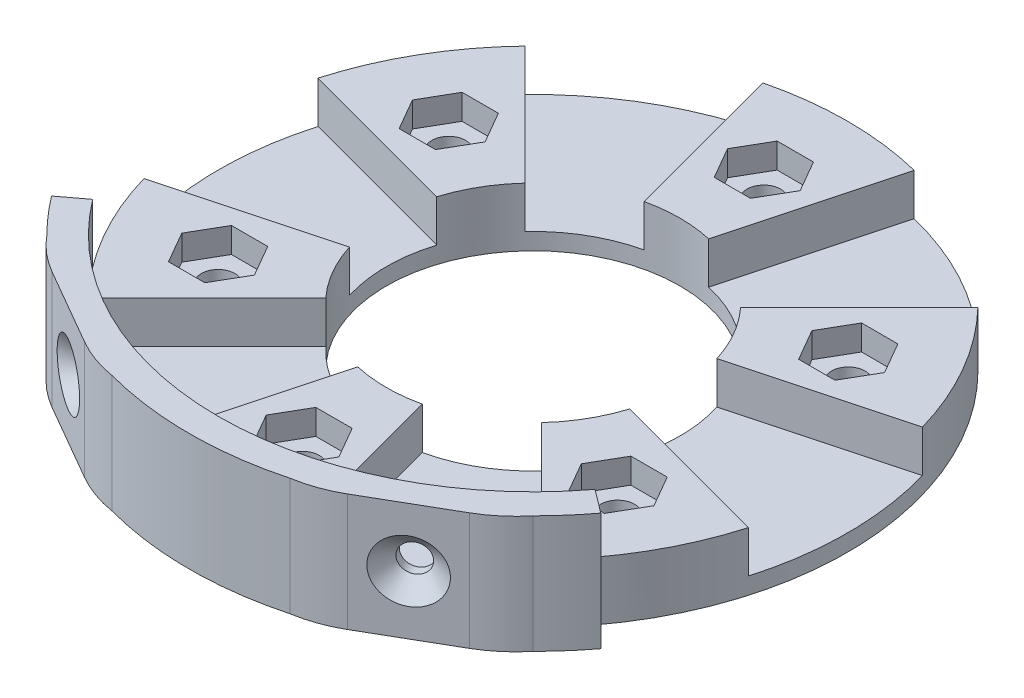
SolidWorks part; units mm, degrees
ref_plane "Front" through (0, 0, 0) normal (0, 0, 1) x (1, 0, 0)
ref_plane "Top" through (0, 0, 0) normal (0, 1, 0) x (1, 0, 0)
ref_plane "Right" through (0, 0, 0) normal (1, 0, 0) x (0, 0, -1)
sketch "Sketch1" plane through (0, 0, 0) normal (0, 1, 0) x (1, 0, 0)
  line L0 (21.6506, 17.5) -> (19.4856, 13.75)
  line L1 (4.3301, 27.5) -> (2.1651, 31.25)
  line L2 (2.1651, 31.25) -> (-2.1651, 31.25)
  line L3 (-2.1651, 31.25) -> (-4.3301, 27.5)
  line L4 (-4.3301, 27.5) -> (-2.1651, 23.75)
  line L5 (-2.1651, 23.75) -> (2.1651, 23.75)
  line L6 (2.1651, 23.75) -> (4.3301, 27.5)
  line L7 (25.9808, 17.5) -> (21.6506, 17.5)
  line L8 (28.1458, 13.75) -> (25.9808, 17.5)
  line L9 (25.9808, 10) -> (28.1458, 13.75)
  line L10 (19.4856, 13.75) -> (21.6506, 10)
  line L11 (21.6506, 10) -> (25.9808, 10)
  line L12 (25.9808, -10) -> (21.6506, -10)
  line L13 (28.1458, -13.75) -> (25.9808, -10)
  line L14 (25.9808, -17.5) -> (28.1458, -13.75)
  line L15 (21.6506, -17.5) -> (25.9808, -17.5)
  line L16 (21.6506, -10) -> (19.4856, -13.75)
  line L17 (19.4856, -13.75) -> (21.6506, -17.5)
  line L18 (4.3301, -27.5) -> (2.1651, -23.75)
  line L19 (2.1651, -31.25) -> (4.3301, -27.5)
  line L20 (-2.1651, -31.25) -> (2.1651, -31.25)
  line L21 (-4.3301, -27.5) -> (-2.1651, -31.25)
  line L22 (2.1651, -23.75) -> (-2.1651, -23.75)
  line L23 (-2.1651, -23.75) -> (-4.3301, -27.5)
  line L24 (-21.6506, -17.5) -> (-19.4856, -13.75)
  line L25 (-25.9808, -17.5) -> (-21.6506, -17.5)
  line L26 (-28.1458, -13.75) -> (-25.9808, -17.5)
  line L27 (-25.9808, -10) -> (-28.1458, -13.75)
  line L28 (-19.4856, -13.75) -> (-21.6506, -10)
  line L29 (-21.6506, -10) -> (-25.9808, -10)
  line L30 (-25.9808, 10) -> (-21.6506, 10)
  line L31 (-28.1458, 13.75) -> (-25.9808, 10)
  line L32 (-25.9808, 17.5) -> (-28.1458, 13.75)
  line L33 (-21.6506, 17.5) -> (-25.9808, 17.5)
  line L34 (-21.6506, 10) -> (-19.4856, 13.75)
  line L35 (-19.4856, 13.75) -> (-21.6506, 17.5)
  line L36 (23.8157, 13.75) -> (15.1554, 8.75)
  line L37 (23.8157, 13.75) -> (32.476, 18.75)
  line L38 (0, 0) -> (9.7057, 36.2222)
  line L39 (0, 0) -> (26.5165, 26.5165)
  line L40 (-9.0279, 36.3971) -> (-3.8496, 17.0713)
  line L41 (26.5165, 26.5165) -> (23.8157, 13.75)
  line L42 (0, 0) -> (36.2222, 9.7057)
  line L43 (0, 0) -> (36.2222, -9.7057)
  line L44 (0, 0) -> (26.5165, -26.5165)
  line L45 (0, 0) -> (9.7057, -36.2222)
  line L46 (0, 0) -> (-9.7057, -36.2222)
  line L47 (0, 0) -> (-26.5165, -26.5165)
  line L48 (0, 0) -> (-36.2222, -9.7057)
  line L49 (0, 0) -> (-36.2222, 9.7057)
  line L50 (0, 0) -> (-26.5165, 26.5165)
  line L51 (0, 0) -> (-9.7057, 36.2222)
  line L52 (0, 0) -> (0, 37.5)
  line L53 (9.0279, 36.3971) -> (3.8496, 17.0713)
  line L54 (27.0069, 26.0169) -> (12.8594, 11.8695)
  line L55 (36.0347, 10.3802) -> (16.709, 5.2019)
  line L56 (36.0347, -10.3802) -> (16.709, -5.2019)
  line L57 (27.0069, -26.0169) -> (12.8594, -11.8695)
  line L58 (9.0279, -36.3971) -> (3.8496, -17.0713)
  line L59 (-9.0279, -36.3971) -> (-3.8496, -17.0713)
  line L60 (-27.0069, -26.0169) -> (-12.8594, -11.8695)
  line L61 (-36.0347, -10.3802) -> (-16.709, -5.2019)
  line L62 (-36.0347, 10.3802) -> (-16.709, 5.2019)
  line L63 (-27.0069, 26.0169) -> (-12.8594, 11.8695)
  circle A0 centre (0, 27.5) radius 2.15
  circle A1 centre (0, 0) radius 37.5
  circle A2 centre (0, 27.5) radius 3.75 construction
  circle A3 centre (23.8157, 13.75) radius 3.75 construction
  circle A4 centre (23.8157, 13.75) radius 2.15
  circle A5 centre (23.8157, -13.75) radius 3.75 construction
  circle A6 centre (23.8157, -13.75) radius 2.15
  circle A7 centre (0, -27.5) radius 3.75 construction
  circle A8 centre (0, -27.5) radius 2.15
  circle A9 centre (-23.8157, -13.75) radius 3.75 construction
  circle A10 centre (-23.8157, -13.75) radius 2.15
  circle A11 centre (-23.8157, 13.75) radius 3.75 construction
  circle A12 centre (-23.8157, 13.75) radius 2.15
  circle A13 centre (0, 0) radius 17.5
  point P60 (0, 0)
  point P75 (0, 0)
  point P101 (0, 0)
  dimension "D1" = 4.3
  dimension "D2" = 75
  dimension "D4" = 7.5
  dimension "D6" = 35
  dimension "D3" = 27.5
  dimension "D7" = 23.8157
  dimension "D8" = 15
  dimension "D10" = 0.7
  dimension "D11" = 0.7
  dimension "D12" = 15
  dimension "D5" = 6
  dimension "D9" = 6
  dimension "D13" = 6
extrude "Boss-Extrude2" add sketch "Sketch1" along normal blind 3 contours A13 L52 L5 L4 L3 L2 A1 L40 | A13 L53 A1 L52 L2 L1 L6 L5 | A13 L63 A1 L62 L35 L34 L30 L31 L32 L33 | A13 L36 L10 L0 L7 L41 L54 | A13 L55 A1 L37 L8 L9 L11 L10 L36 | L37 A1 L54 L41 L7 L8 | A13 L57 A1 L56 L17 L16 L12 L13 L14 L15 | A13 L59 A1 L58 L23 L22 L18 L19 L20 L21 | A13 L61 A1 L60 L29 L28 L24 L25 L26 L27
sketch "Sketch2" plane through (0, 0, 0) normal (0, -1, 0) x (-1, 0, 0)
  line L12 (16.709, 5.2019) -> (36.0347, 10.3802) construction
  line L13 (27.0069, 26.0169) -> (12.8594, 11.8695) construction
  line L14 (3.8496, 17.0713) -> (9.0279, 36.3971) construction
  line L15 (-9.0279, 36.3971) -> (-3.8496, 17.0713) construction
  line L16 (-36.0347, 10.3802) -> (-16.709, 5.2019) construction
  line L17 (-12.8594, 11.8695) -> (-27.0069, 26.0169) construction
  line L18 (-16.709, -5.2019) -> (-36.0347, -10.3802) construction
  line L19 (-27.0069, -26.0169) -> (-12.8594, -11.8695) construction
  line L20 (-3.8496, -17.0713) -> (-9.0279, -36.3971) construction
  line L21 (9.0279, -36.3971) -> (3.8496, -17.0713) construction
  line L22 (12.8594, -11.8695) -> (27.0069, -26.0169) construction
  line L23 (36.0347, -10.3802) -> (16.709, -5.2019) construction
  line L24 (16.709, 5.2019) -> (36.0347, 10.3802)
  line L25 (27.0069, 26.0169) -> (12.8594, 11.8695)
  line L26 (3.8496, 17.0713) -> (9.0279, 36.3971)
  line L27 (-9.0279, 36.3971) -> (-3.8496, 17.0713)
  line L28 (-36.0347, 10.3802) -> (-16.709, 5.2019)
  line L29 (-12.8594, 11.8695) -> (-27.0069, 26.0169)
  line L30 (-16.709, -5.2019) -> (-36.0347, -10.3802)
  line L31 (-27.0069, -26.0169) -> (-12.8594, -11.8695)
  line L32 (-3.8496, -17.0713) -> (-9.0279, -36.3971)
  line L33 (9.0279, -36.3971) -> (3.8496, -17.0713)
  line L34 (12.8594, -11.8695) -> (27.0069, -26.0169)
  line L35 (36.0347, -10.3802) -> (16.709, -5.2019)
  circle A0 centre (0, 0) radius 37.5
  circle A1 centre (0, 0) radius 17.5
  circle A2 centre (0, 27.5) radius 2
  circle A3 centre (23.8157, 13.75) radius 2
  circle A4 centre (23.8157, -13.75) radius 2
  circle A5 centre (0, -27.5) radius 2
  circle A6 centre (-23.8157, -13.75) radius 2
  circle A7 centre (-23.8157, 13.75) radius 2
  arc A8 (16.709, 5.2019) -> (12.8594, 11.8695) centre (0, 0) ccw construction
  arc A9 (36.0347, 10.3802) -> (27.0069, 26.0169) centre (0, 0) ccw construction
  arc A10 (3.8496, 17.0713) -> (-3.8496, 17.0713) centre (0, 0) ccw construction
  arc A11 (9.0279, 36.3971) -> (-9.0279, 36.3971) centre (0, 0) ccw construction
  arc A12 (-12.8594, 11.8695) -> (-16.709, 5.2019) centre (0, 0) ccw construction
  arc A13 (-27.0069, 26.0169) -> (-36.0347, 10.3802) centre (0, 0) ccw construction
  arc A14 (-16.709, -5.2019) -> (-12.8594, -11.8695) centre (0, 0) ccw construction
  arc A15 (-36.0347, -10.3802) -> (-27.0069, -26.0169) centre (0, 0) ccw construction
  arc A16 (-3.8496, -17.0713) -> (3.8496, -17.0713) centre (0, 0) ccw construction
  arc A17 (-9.0279, -36.3971) -> (9.0279, -36.3971) centre (0, 0) ccw construction
  arc A18 (12.8594, -11.8695) -> (16.709, -5.2019) centre (0, 0) ccw construction
  arc A19 (27.0069, -26.0169) -> (36.0347, -10.3802) centre (0, 0) ccw construction
  arc A20 (16.709, 5.2019) -> (12.8594, 11.8695) centre (0, 0) ccw
  arc A21 (36.0347, 10.3802) -> (27.0069, 26.0169) centre (0, 0) ccw
  arc A22 (3.8496, 17.0713) -> (-3.8496, 17.0713) centre (0, 0) ccw
  arc A23 (9.0279, 36.3971) -> (-9.0279, 36.3971) centre (0, 0) ccw
  arc A24 (-12.8594, 11.8695) -> (-16.709, 5.2019) centre (0, 0) ccw
  arc A25 (-27.0069, 26.0169) -> (-36.0347, 10.3802) centre (0, 0) ccw
  arc A26 (-16.709, -5.2019) -> (-12.8594, -11.8695) centre (0, 0) ccw
  arc A27 (-36.0347, -10.3802) -> (-27.0069, -26.0169) centre (0, 0) ccw
  arc A28 (-3.8496, -17.0713) -> (3.8496, -17.0713) centre (0, 0) ccw
  arc A29 (-9.0279, -36.3971) -> (9.0279, -36.3971) centre (0, 0) ccw
  arc A30 (12.8594, -11.8695) -> (16.709, -5.2019) centre (0, 0) ccw
  arc A31 (27.0069, -26.0169) -> (36.0347, -10.3802) centre (0, 0) ccw
  point P18 (0, 0)
  dimension "D1" = 4
  dimension "D4" = 75
  dimension "D5" = 35
  dimension "D2" = 27.5
  dimension "D6" = 23.8157
  dimension "D7" = 13.75
  dimension "D3" = 6
extrude "Boss-Extrude3" add sketch "Sketch2" along normal blind 2
sketch "Sketch3" plane through (0, -2, 0) normal (0, -1, 0) x (-1, 0, 0)
  circle A0 centre (0, 0) radius 37.5
  circle A1 centre (0, 0) radius 17.5
  circle A2 centre (0, 27.5) radius 2
  circle A3 centre (23.8157, 13.75) radius 2
  circle A4 centre (23.8157, -13.75) radius 2
  circle A5 centre (0, -27.5) radius 2
  circle A6 centre (-23.8157, -13.75) radius 2
  circle A7 centre (-23.8157, 13.75) radius 2
  point P19 (0, 0)
  dimension "D1" = 6
extrude "Boss-Extrude4" add sketch "Sketch3" along normal blind 2
sketch "Sketch4" plane through (0, -4, 0) normal (0, -1, 0) x (-1, 0, 0)
  line L0 (0, 0) -> (32.7404, -24.6793)
  line L1 (0, 0) -> (-32.7404, -24.6793)
  line L2 (28.9914, -28.9914) -> (0, 0)
  line L3 (-28.9914, -28.9914) -> (0, 0)
  line L6 (0, 0) -> (10.6116, -39.603)
  line L7 (0, 0) -> (-10.6116, -39.603)
  line L10 (10.6116, -39.603) -> (10.8704, -40.5689)
  line L11 (28.9914, -28.9914) -> (29.6985, -29.6985)
  line L12 (-10.6116, -39.603) -> (-10.8704, -40.5689)
  line L13 (-28.9914, -28.9914) -> (-29.6985, -29.6985)
  line L14 (-29.6985, -29.6985) -> (-10.8704, -40.5689)
  line L15 (10.8704, -40.5689) -> (29.6985, -29.6985)
  line L16 (-27.0069, -26.0169) -> (-12.8594, -11.8695) construction
  line L17 (12.8594, -11.8695) -> (27.0069, -26.0169) construction
  line L18 (-3.8496, -17.0713) -> (-9.0279, -36.3971) construction
  line L19 (9.0279, -36.3971) -> (3.8496, -17.0713) construction
  circle A0 centre (0, 0) radius 37.5
  circle A1 centre (0, 0) radius 41
  dimension "D1" = 82
  dimension "D2" = 75
  dimension "D3" = 5
  dimension "D4" = 5
  dimension "D5" = 1
  dimension "D6" = 1
  dimension "D7" = 1
  dimension "D8" = 1
extrude "Boss-Extrude5" add sketch "Sketch4" against normal blind 14
fillet "Fillet1" radius 15 4 edges at (29.6985, 3, 29.6985) (10.8704, 3, 40.5689) (-29.6985, 3, 29.6985) (-10.8704, 3, 40.5689)
sketch "Sketch6" plane through (20.2844, 0, 35.1337) normal (0.5, 0, 0.866) x (0.866, 0, -0.5)
  line L1 (0, 3) -> (0, 10)
  line L2 (5.3159, 10) -> (-5.3159, 10) construction
  line L4 (0, 3) -> (-5.3159, 3)
  line L5 (0, 3) -> (0, -4)
  line L6 (5.3159, -4) -> (-5.3159, -4) construction
  line L7 (-5.3159, 10) -> (-5.3159, -4) construction
  line L8 (0, 3) -> (5.3159, 3)
  line L9 (5.3159, -4) -> (5.3159, 10) construction
  circle A0 centre (0, 3) radius 1.65
  dimension "D1" = 3.3
extrude "Cut-Extrude1" cut sketch "Sketch6" against normal blind 4 contours L5 A0 L8 | L4 A0 L5 | L8 A0 L1 | L1 A0 L4
sketch "Sketch7" plane through (-20.2844, 0, 35.1337) normal (-0.5, 0, 0.866) x (0.866, 0, 0.5)
  line L1 (0, 3) -> (0, 10)
  line L4 (5.3159, 10) -> (-5.3159, 10) construction
  line L8 (0, 3) -> (0, -4)
  line L9 (5.3159, -4) -> (-5.3159, -4) construction
  line L10 (0, 3) -> (-5.3159, 3)
  line L11 (-5.3159, 10) -> (-5.3159, -4) construction
  line L12 (0, 3) -> (5.3159, 3)
  line L13 (5.3159, -4) -> (5.3159, 10) construction
  line L15 (10.3802, -2) -> (-10.3802, -2) construction
  circle A0 centre (0, 3) radius 1.65
  dimension "D1" = 3.3
  dimension "D2" = 5
extrude "Cut-Extrude2" cut sketch "Sketch7" against normal blind 4 contours L8 A0 L12 | L10 A0 L8 | L1 A0 L10 | L12 A0 L1
chamfer "Chamfer2" distance 2 distance2 2 2 edges at (-18.8555, 3, 35.9587) (21.7134, 3, 34.3087)
